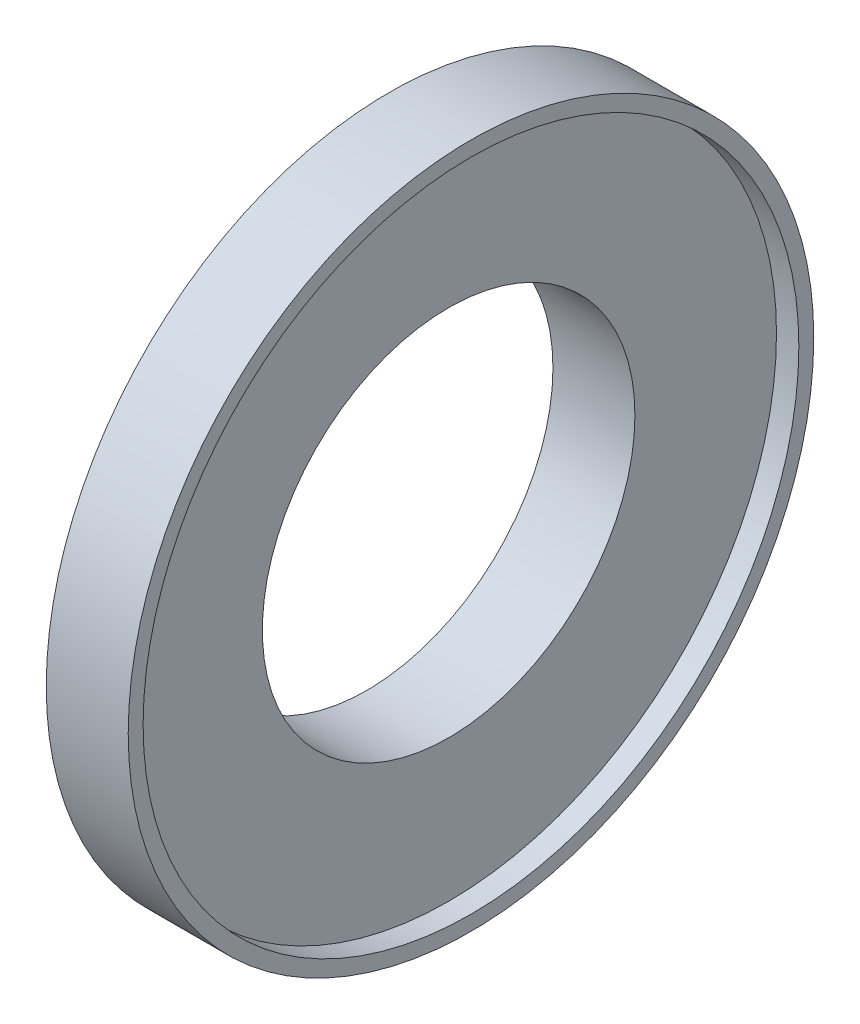
SolidWorks part; units mm, degrees
material "Silicon Rubber"
ref_plane "Front Plane" through (0, 0, 0) normal (0, 0, 1) x (1, 0, 0)
ref_plane "Top Plane" through (0, 0, 0) normal (0, 1, 0) x (1, 0, 0)
ref_plane "Right Plane" through (0, 0, 0) normal (1, 0, 0) x (0, 0, -1)
sketch "Sketch1" plane through (0, 0, 0) normal (1, 0, 0) x (0, 0, -1)
  circle A0 centre (0, 0) radius 5.842
  dimension "D1" = 11.684
extrude "Boss-Extrude1" add sketch "Sketch1" along normal blind 1.397
sketch "Sketch2" plane through (1.397, 0, 0) normal (1, 0, 0) x (0, 0, -1)
  circle A0 centre (0, 0) radius 5.588
  dimension "D1" = 11.176
extrude "Cut-Extrude1" cut sketch "Sketch2" against normal blind 0.381
sketch "Sketch3" plane through (1.016, 0, 0) normal (1, 0, 0) x (0, 0, -1)
  circle A0 centre (0, 0) radius 3.175
  dimension "D1" = 6.35
extrude "Cut-Extrude2" cut sketch "Sketch3" against normal through all
sketch "Sketch4" plane through (0, 0, 0) normal (-1, 0, 0) x (0, 0, 1)
  circle A0 centre (0, 0) radius 3.81
  dimension "D1" = 7.62
extrude "Boss-Extrude2" add sketch "Sketch4" along normal blind 0.381
chamfer "Chamfer1" distance 0.381 angle 45 1 edges at (0, 0, -3.81)
sketch "Sketch5" plane through (0, 0, 0) normal (1, 0, 0) x (0, 0, -1)
  circle A0 centre (0, 0) radius 3.175
extrude "Cut-Extrude3" cut sketch "Sketch5" against normal through all
